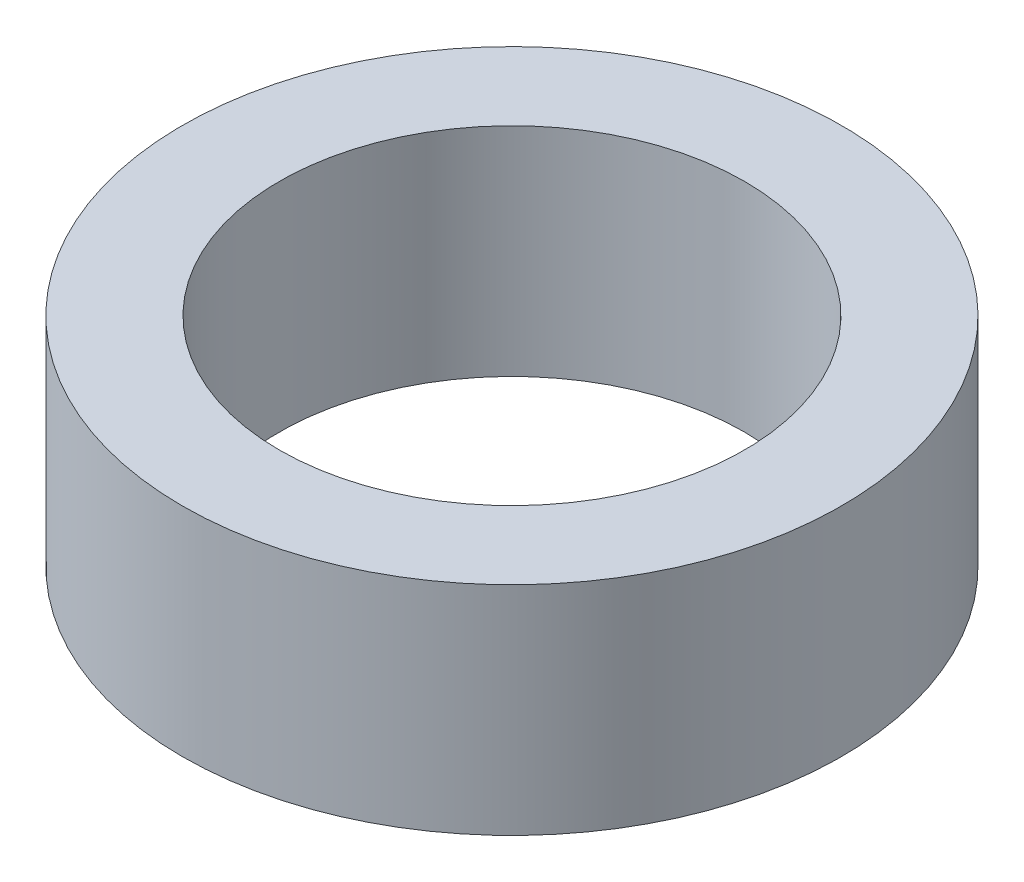
SolidWorks part; units mm, degrees
ref_plane "Front Plane" through (0, 0, 0) normal (0, 0, 1) x (1, 0, 0)
ref_plane "Top Plane" through (0, 0, 0) normal (0, 1, 0) x (1, 0, 0)
ref_plane "Right Plane" through (0, 0, 0) normal (1, 0, 0) x (0, 0, -1)
sketch "Sketch1" plane through (0, 0, 0) normal (0, 1, 0) x (1, 0, 0)
  circle A0 centre (0, 0) radius 42.5
  dimension "FLANGE_OD" = 85
extrude "Boss-Extrude1" add sketch "Sketch1" along normal blind 28
sketch "Sketch2" plane through (0, 0, 0) normal (0, 1, 0) x (1, 0, 0)
  circle A0 centre (0, 0) radius 30
  dimension "BORE_D" = 60
extrude "Cut-Extrude1" cut sketch "Sketch2" along normal through all
sketch "Sketch3" plane through (0, 28, 0) normal (0, 1, 0) x (1, 0, 0)
  circle A0 centre (0, 0) radius 17.8129 construction
  circle A1 centre (-17.8129, 0) radius 2.084
  dimension "BOLT_D" = 4.168
  dimension "BOLT_PCD" = 35.6258
extrude "Cut-Extrude2" cut sketch "Sketch3" against normal blind 26.7313 rebuild error yes
pattern_circular "CirPattern1" count 5 over 360 rebuild error yes
